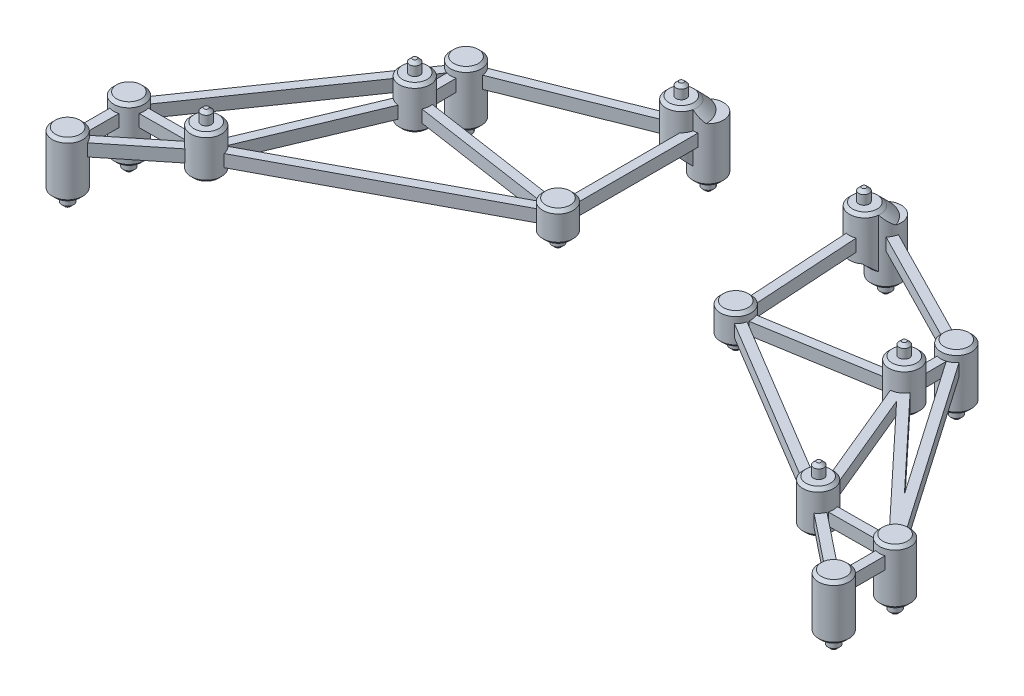
SolidWorks part; units mm, degrees
ref_plane "정면" through (0, 0, 0) normal (0, 0, 1) x (1, 0, 0)
ref_plane "윗면" through (0, 0, 0) normal (0, 1, 0) x (1, 0, 0)
ref_plane "우측면" through (0, 0, 0) normal (1, 0, 0) x (0, 0, -1)
sketch "스케치1" plane through (0, 0, 0) normal (0, 1, 0) x (1, 0, 0)
  line L0 (-33.4243, 0) -> (38.4886, 0) construction
  line L1 (0, -25.0682) -> (0, 57.4797) construction
  circle A0 centre (-25, 124) radius 5 construction
  circle A1 centre (-25, 124) radius 5
  circle A4 centre (-80, 100) radius 5 construction
  circle A5 centre (-80, 100) radius 5
  circle A6 centre (-125, 35) radius 5 construction
  circle A7 centre (-125, 35) radius 5
  circle A8 centre (-125, 15) radius 5 construction
  circle A9 centre (-125, 15) radius 5
  circle A10 centre (125, 15) radius 5
  circle A11 centre (125, 35) radius 5
  circle A12 centre (80, 100) radius 5
  circle A15 centre (33, 124) radius 5 construction
  circle A16 centre (33, 124) radius 5
extrude "보스-돌출1" add sketch "스케치1" along normal blind 8
sketch "스케치2" plane through (0, 8, 0) normal (0, 1, 0) x (1, 0, 0)
  line L0 (53.6121, 0) -> (-76.5516, 0) construction
  line L1 (0, -49.2613) -> (0, 97.446) construction
  circle A0 centre (-125, 15) radius 5 construction
  circle A1 centre (-125, 35) radius 5 construction
  circle A2 centre (-80, 100) radius 5 construction
  circle A3 centre (-25, 124) radius 5 construction
  circle A4 centre (-125, 15) radius 5
  circle A5 centre (-125, 35) radius 5
  circle A6 centre (-80, 100) radius 5
  circle A7 centre (-25, 124) radius 5
  circle A8 centre (125, 15) radius 5 construction
  circle A9 centre (125, 35) radius 5 construction
  circle A10 centre (80, 100) radius 5 construction
  circle A11 centre (33, 124) radius 5 construction
  circle A12 centre (125, 15) radius 5
  circle A13 centre (125, 35) radius 5
  circle A14 centre (80, 100) radius 5
  circle A15 centre (33, 124) radius 5
  circle A16 centre (33, 75) radius 5 construction
  circle A17 centre (33, 75) radius 5
  circle A18 centre (-25, 75) radius 5 construction
  circle A19 centre (-25, 75) radius 5
extrude "보스-돌출2" add sketch "스케치2" along normal blind 10
sketch "스케치4" plane through (0, 18, 0) normal (0, 1, 0) x (1, 0, 0)
  circle A0 centre (80.1349, 82.8698) radius 5 construction
  circle A1 centre (80.1349, 82.8698) radius 5
  circle A2 centre (100.0568, 34.8373) radius 5 construction
  circle A3 centre (100.0568, 34.8373) radius 5
  circle A4 centre (-29.8048, 120.0487) radius 5 construction
  circle A5 centre (-29.8048, 120.0487) radius 5
  circle A6 centre (30.1951, 119.9511) radius 5 construction
  circle A7 centre (30.1951, 119.9511) radius 5
  circle A8 centre (-79.8649, 83.13) radius 5 construction
  circle A9 centre (-79.8649, 83.13) radius 5
  circle A10 centre (-99.9429, 35.1626) radius 5 construction
  circle A11 centre (-99.9429, 35.1626) radius 5
extrude "보스-돌출3" add sketch "스케치4" along normal blind 4 and the other way blind 10
sketch "스케치5" plane through (0, 18, 0) normal (0, 1, 0) x (1, 0, 0)
  line L0 (-125, 35) -> (-80, 100) construction
  line L1 (-80, 100) -> (-29.8048, 120.0487) construction
  line L2 (-29.8048, 120.0487) -> (-25, 124) construction
  line L3 (-25, 124) -> (-25, 75) construction
  line L4 (-25, 75) -> (-79.8649, 83.13) construction
  line L5 (-79.8649, 83.13) -> (-99.9429, 35.1626) construction
  line L6 (-99.9429, 35.1626) -> (-125, 15) construction
  line L7 (-125, 15) -> (-125, 35) construction
  line L8 (-125, 35) -> (-99.9429, 35.1626) construction
  line L9 (-80, 100) -> (-79.8649, 83.13) construction
  line L10 (-25, 75) -> (-99.9429, 35.1626) construction
  line L11 (33, 124) -> (30.1951, 119.9511) construction
  line L12 (30.1951, 119.9511) -> (33, 75) construction
  line L13 (33, 75) -> (100.0568, 34.8373) construction
  line L14 (100.0568, 34.8373) -> (125, 15) construction
  line L15 (125, 15) -> (125, 35) construction
  line L16 (125, 35) -> (80.1349, 82.8698) construction
  line L17 (80.1349, 82.8698) -> (80, 100) construction
  line L18 (80, 100) -> (33, 124) construction
  line L19 (80, 100) -> (125, 35) construction
  line L20 (125, 35) -> (100.0568, 34.8373) construction
  line L21 (100.0568, 34.8373) -> (80.1349, 82.8698) construction
  line L22 (80.1349, 82.8698) -> (33, 75) construction
  line L23 (-29.7299, 74.1845) -> (-96.9369, 38.4593)
  line L24 (-104.2344, 33.6347) -> (-123.5, 18.1323)
  line L25 (-123.5, 18.1323) -> (-123.5, 33.5097)
  line L26 (-123.5, 33.5097) -> (-104.2344, 33.6347)
  line L27 (-126.2333, 35.8538) -> (-126.5, 35)
  line L28 (-81.3673, 83.4255) -> (-100.9439, 36.6561)
  line L29 (-81.462, 95.2529) -> (-81.3673, 83.4255)
  line L30 (-29.7299, 74.1845) -> (-78.9314, 81.4753)
  line L31 (-78.4812, 82.5508) -> (-98.5593, 34.5834) construction
  line L32 (-29.032, 118.7421) -> (-26.5, 120.8244)
  line L33 (-26.5, 120.8244) -> (-26.5, 76.7387)
  line L34 (32.2293, 73.7132) -> (99.2009, 33.6015)
  line L35 (80.6822, 101.3359) -> (32.5139, 125.9325)
  line L36 (32.5139, 125.9325) -> (28.6656, 120.3773)
  line L37 (28.6656, 120.3773) -> (31.5029, 74.9066)
  line L38 (81.5383, 95.1428) -> (112.2077, 50.8425)
  line L39 (81.6302, 83.4678) -> (81.5383, 95.1428)
  line L40 (78.6248, 84.1384) -> (34.3935, 76.7534)
  line L41 (101.0558, 36.3439) -> (84.6799, 75.8269)
  line L42 (99.2009, 33.6015) -> (126.5, 11.8905)
  line L43 (126.5, 11.8905) -> (126.5, 35)
  line L44 (126.2333, 35.8538) -> (126.5, 35)
  line L45 (123.5, 34.9902) -> (123.5, 35)
  line L46 (-24.2959, 73.6755) -> (-99.1133, 33.9048)
  line L47 (-99.1133, 33.9048) -> (-126.5, 11.8677)
  line L48 (-126.5, 11.8677) -> (-126.5, 35)
  line L50 (-126.2333, 35.8538) -> (-81.2333, 100.8538)
  line L51 (-78.9314, 81.4753) -> (-96.9369, 38.4593)
  line L52 (-78.4918, 98.9872) -> (-78.3752, 84.4256)
  line L53 (-80.5564, 101.393) -> (-81.2333, 100.8538)
  line L54 (-80.5564, 101.393) -> (-30.5776, 121.3552)
  line L55 (-30.5776, 121.3552) -> (-23.5, 127.1756)
  line L56 (-23.5, 127.1756) -> (-23.5, 75)
  line L57 (32.2293, 73.7132) -> (31.5029, 74.9066)
  line L58 (81.6348, 82.8816) -> (81.5, 100.0118) construction
  line L59 (33.4861, 122.0675) -> (31.7246, 119.5249)
  line L60 (31.7246, 119.5249) -> (34.3935, 76.7534)
  line L61 (81.2333, 100.8538) -> (126.2333, 35.8538)
  line L62 (78.6248, 84.1384) -> (78.5072, 99.078)
  line L63 (79.2061, 81.1939) -> (37.2685, 74.1919)
  line L64 (32.2293, 73.7132) -> (99.2861, 33.5505) construction
  line L65 (96.9313, 38.4578) -> (79.2061, 81.1939)
  line L66 (123.5, 18.1095) -> (123.5, 33.4902)
  line L67 (123.5, 33.4902) -> (104.3178, 33.3651)
  line L68 (125.0098, 33.5) -> (125, 33.5)
  line L69 (80.6822, 101.3359) -> (81.2333, 100.8538)
  line L70 (78.6349, 82.858) -> (78.5, 99.9882) construction
  line L71 (78.7667, 99.1462) -> (123.7667, 34.1462) construction
  line L72 (78.5072, 99.078) -> (33.4861, 122.0675)
  line L73 (79.3178, 98.6641) -> (33.4861, 122.0675) construction
  line L74 (104.3178, 33.3651) -> (123.5, 18.1095)
  line L75 (80.3819, 81.3903) -> (33.247, 73.5205) construction
  line L76 (101.4423, 35.412) -> (81.5204, 83.4444) construction
  line L77 (99.1231, 33.6633) -> (126.5, 11.8905) construction
  line L78 (125.0098, 33.5) -> (100.0666, 33.3373) construction
  line L79 (79.8879, 84.3493) -> (32.753, 76.4795) construction
  line L80 (112.2077, 50.8425) -> (81.6302, 83.4678)
  line L81 (100.9905, 36.0113) -> (123.5, 18.1095) construction
  line L82 (121.5593, 36.4776) -> (101.0558, 36.3439)
  line L83 (123.5, 18.1095) -> (123.5, 35) construction
  line L84 (121.5593, 36.4776) -> (84.6799, 75.8269)
  line L85 (-23.5, 75) -> (-24.2959, 73.6755)
  line L86 (-26.5, 76.7387) -> (-78.3752, 84.4256)
  line L87 (37.2685, 74.1919) -> (96.9313, 38.4578)
  line L88 (-81.5, 99.988) -> (-81.3648, 83.118) construction
  line L89 (-81.2486, 83.7092) -> (-101.3266, 35.7418) construction
  line L90 (31.7246, 119.5249) -> (34.4971, 75.0934) construction
  line L91 (-25.7041, 76.3245) -> (-100.647, 36.4871) construction
  line L92 (-100.8833, 36.3312) -> (-123.5, 18.1323) construction
  line L93 (-26.5, 120.8244) -> (-26.5, 75) construction
  line L95 (-78.5, 100.012) -> (-78.3649, 83.142) construction
  line L96 (-78.4918, 98.9872) -> (-29.032, 118.7421)
  line L97 (-79.4436, 98.607) -> (-29.032, 118.7421) construction
  line L98 (-99.0026, 33.994) -> (-126.5, 11.8677) construction
  line L101 (-124.9903, 33.5) -> (-99.9332, 33.6626) construction
  line L102 (-24.2959, 73.6755) -> (-99.2389, 33.8381) construction
  line L103 (-122.1242, 36.5187) -> (-81.462, 95.2529)
  line L104 (-122.1242, 36.5187) -> (-100.9439, 36.6561)
  line L106 (-123.5, 18.1323) -> (-123.5, 35) construction
  circle A0 centre (-125, 15) radius 5 construction
  circle A1 centre (125, 15) radius 5
  circle A2 centre (125, 15) radius 5 construction
  circle A3 centre (-125, 35) radius 5 construction
  circle A4 centre (-99.9429, 35.1626) radius 5 construction
  circle A5 centre (-79.8649, 83.13) radius 5 construction
  circle A6 centre (-80, 100) radius 5 construction
  circle A7 centre (-29.8048, 120.0487) radius 5 construction
  arc A8 (-24.9158, 119.0007) -> (-29.8889, 125.048) centre (-29.8048, 120.0487) ccw construction
  arc A9 (-24.9158, 119.0007) -> (-29.8889, 125.048) centre (-25, 124) ccw construction
  circle A10 centre (-25, 75) radius 5 construction
  circle A11 centre (33, 75) radius 5 construction
  circle A12 centre (30.1951, 119.9511) radius 5 construction
  arc A13 (35.1745, 119.4976) -> (28.0206, 124.4535) centre (30.1951, 119.9511) ccw construction
  arc A14 (35.1745, 119.4976) -> (28.0206, 124.4535) centre (33, 124) ccw construction
  circle A15 centre (80, 100) radius 5 construction
  circle A16 centre (80.1349, 82.8698) radius 5 construction
  circle A17 centre (100.0568, 34.8373) radius 5 construction
  circle A18 centre (125, 35) radius 5 construction
  circle A19 centre (-125, 15) radius 5 construction
  circle A20 centre (-125, 35) radius 5 construction
  circle A21 centre (-99.9429, 35.1626) radius 5 construction
  circle A22 centre (-79.8649, 83.13) radius 5 construction
  circle A23 centre (-80, 100) radius 5 construction
  circle A24 centre (-29.8048, 120.0487) radius 5 construction
  arc A25 (-24.9158, 119.0007) -> (-29.8889, 125.048) centre (-29.8048, 120.0487) ccw construction
  arc A26 (-24.9158, 119.0007) -> (-29.8889, 125.048) centre (-25, 124) ccw construction
  circle A27 centre (-25, 75) radius 5 construction
  circle A28 centre (33, 75) radius 5 construction
  circle A29 centre (30.1951, 119.9511) radius 5 construction
  arc A30 (35.1745, 119.4976) -> (28.0206, 124.4535) centre (30.1951, 119.9511) ccw construction
  arc A31 (35.1745, 119.4976) -> (28.0206, 124.4535) centre (33, 124) ccw construction
  circle A32 centre (80, 100) radius 5 construction
  circle A33 centre (80.1349, 82.8698) radius 5 construction
  circle A34 centre (100.0568, 34.8373) radius 5 construction
  circle A35 centre (125, 35) radius 5 construction
  dimension "D1" = 0
  dimension "D2" = 1.5
  dimension "D3" = 1.5
extrude "보스-돌출4" add sketch "스케치5" against normal blind 4 from offset 3 offset against normal yes
sketch "스케치6" plane through (0, 8, 0) normal (0, -1, 0) x (1, 0, 0)
  circle A2 centre (-25, -75) radius 1.9
  circle A3 centre (-25, -75) radius 1.9
  circle A5 centre (33, -75) radius 1.9
  circle A6 centre (33, -75) radius 1.9
  dimension "D1" = 3.1
  dimension "D2" = 3.1
extrude "보스-돌출5" add sketch "스케치6" along normal blind 3.5
sketch "스케치7" plane through (0, 0, 0) normal (0, -1, 0) x (1, 0, 0)
  circle A2 centre (33, -124) radius 1.9
  circle A3 centre (33, -124) radius 1.9
  circle A5 centre (-25, -124) radius 1.9
  circle A6 centre (-25, -124) radius 1.9
  circle A8 centre (-80, -100) radius 1.9
  circle A9 centre (-80, -100) radius 1.9
  circle A11 centre (-125, -35) radius 1.9
  circle A12 centre (-125, -35) radius 1.9
  circle A14 centre (-125, -15) radius 1.9
  circle A15 centre (-125, -15) radius 1.9
  circle A17 centre (125, -35) radius 1.9
  circle A18 centre (125, -35) radius 1.9
  circle A20 centre (80, -100) radius 1.9
  circle A21 centre (80, -100) radius 1.9
  circle A23 centre (125, -15) radius 1.9
  circle A24 centre (125, -15) radius 1.9
  dimension "D1" = 3.1
  dimension "D2" = 3.1
  dimension "D3" = 3.1
  dimension "D4" = 3.1
  dimension "D5" = 3.1
  dimension "D6" = 3.1
  dimension "D7" = 3.1
  dimension "D8" = 3.1
extrude "보스-돌출6" add sketch "스케치7" along normal blind 4
sketch "스케치8" plane through (0, 22, 0) normal (0, 1, 0) x (1, 0, 0)
  line L0 (0, 90.5862) -> (0, -57.4134) construction
  circle A2 centre (-99.9429, 35.1626) radius 1.7
  circle A3 centre (-99.9429, 35.1626) radius 1.7
  circle A5 centre (-79.8649, 83.13) radius 1.7
  circle A6 centre (-79.8649, 83.13) radius 1.7
  circle A7 centre (29.8048, 120.0487) radius 1.7
  circle A8 centre (-29.8048, 120.0487) radius 1.7
  circle A9 centre (-29.8048, 120.0487) radius 1.7
  circle A10 centre (79.8649, 83.13) radius 1.7
  circle A11 centre (99.9429, 35.1626) radius 1.7
  dimension "D1" = 3.3
  dimension "D2" = 3.3
  dimension "D3" = 3.3
extrude "보스-돌출7" add sketch "스케치8" along normal blind 4
chamfer "모따기1" distance 1 angle 45 22 edges at (-25, 4.5, -76.9) (-25, -4, -125.9) (-80, -4, -101.9) (-125, -4, -36.9) (-125, -4, -16.9) (-29.8048, 26, -118.3487) (-79.8649, 26, -81.43) (-99.9429, 26, -33.4626) (-125, 18, -30) (-125, 18, -10) (-80, 18, -95) (-25, 18, -70) (-99.9429, 22, -30.1626) (-79.8649, 22, -78.13) (-79.8649, 8, -78.13) (-25, 8, -70) (-99.9429, 8, -30.1626) (-125, 0, -10) (-125, 0, -30) (-80, 0, -95) (-29.8048, 22, -115.0487) (-25, 0, -119)
chamfer "모따기2" distance 1 angle 45 22 edges at (29.8048, 26, -121.7487) (99.9429, 26, -36.8626) (79.8649, 26, -84.83) (125, -4, -16.9) (125, -4, -36.9) (33, 4.5, -76.9) (80, -4, -101.9) (33, -4, -125.9) (125, 18, -10) (125, 18, -30) (80, 18, -95) (33, 18, -70) (80.1349, 8, -77.8698) (80.1349, 22, -77.8698) (30.1951, 22, -114.9511) (100.0568, 22, -29.8373) (80, 0, -105) (33, 8, -70) (33, 0, -119) (100.0568, 8, -29.8373) (125, 0, -20) (125, 0, -40)
chamfer "모따기3" distance 3 angle 45 2 edges at (30.1527, 8, -119.8899) (33.0424, 18, -124.0612)
chamfer "모따기4" distance 3 angle 45 2 edges at (-25.9429, 18, -123.2245) (-28.8618, 8, -120.8241)
